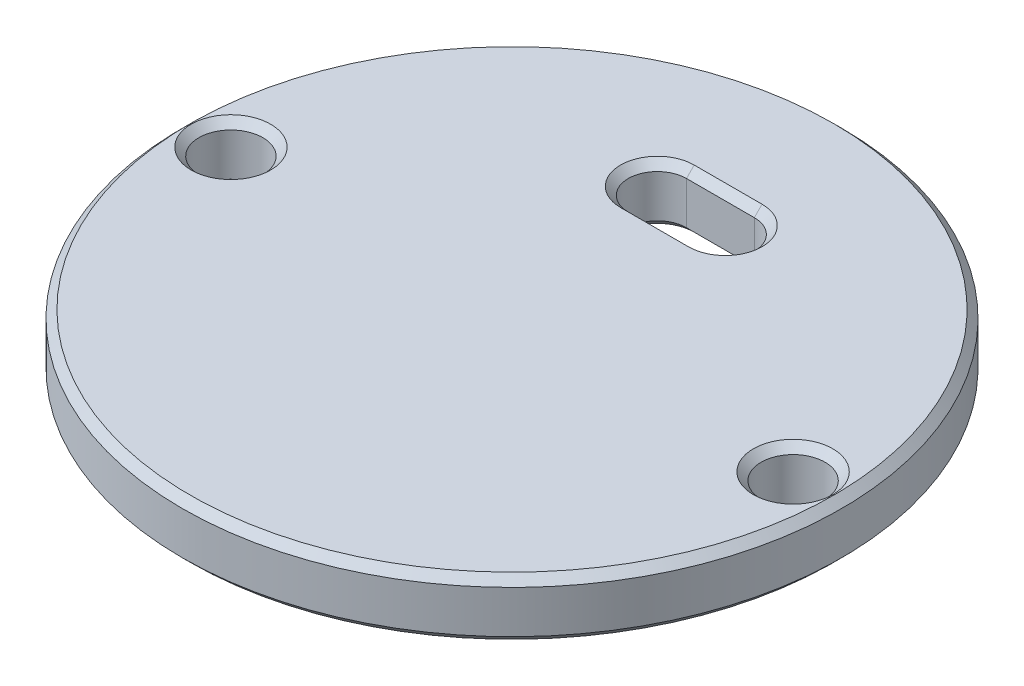
SolidWorks part; units mm, degrees
material "Pine"
ref_plane "Front Plane" through (0, 0, 0) normal (0, 0, 1) x (1, 0, 0)
ref_plane "Top Plane" through (0, 0, 0) normal (0, 1, 0) x (1, 0, 0)
ref_plane "Right Plane" through (0, 0, 0) normal (1, 0, 0) x (0, 0, -1)
sketch "Sketch1" plane through (0, 0, 0) normal (0, 1, 0) x (1, 0, 0)
  line L0 (-1.75, 9.083) -> (-1.75, 10.75) construction
  line L1 (-1.75, 7.75) -> (1.75, 7.75)
  line L2 (-1.75, 7.75) -> (-1.75, 9.083) construction
  line L3 (-1.75, 10.75) -> (1.75, 10.75)
  line L4 (1.75, 7.75) -> (1.75, 9.083) construction
  line L5 (-1.75, 7.75) -> (-0.2676, 9.0206) construction
  line L6 (-1.75, 10.75) -> (-0.2676, 9.4794) construction
  line L7 (-0.2676, 9.4794) -> (0, 9.25) construction
  line L8 (0.2676, 9.0206) -> (1.75, 7.75) construction
  line L9 (0, 9.25) -> (0.2676, 9.4794) construction
  line L10 (0.2676, 9.4794) -> (1.75, 10.75) construction
  line L11 (1.75, 9.083) -> (1.75, 10.75) construction
  line L12 (0, 9.25) -> (0.2676, 9.0206) construction
  line L13 (-0.2676, 9.0206) -> (0, 9.25) construction
  line L14 (-14.5, 0) -> (14.5, 0) construction
  circle A0 centre (0, 0) radius 17
  circle A1 centre (0, 0) radius 9.25 construction
  arc A2 (1.75, 7.75) -> (1.75, 10.75) centre (1.75, 9.25) ccw
  arc A3 (-1.75, 10.75) -> (-1.75, 7.75) centre (-1.75, 9.25) ccw
  arc A4 (-0.25, 9.2466) -> (-0.2676, 9.4794) centre (-1.75, 9.25) ccw construction
  arc A5 (-0.2676, 9.4794) -> (-1.75, 10.75) centre (-1.75, 9.25) ccw construction
  arc A6 (0.2676, 9.4794) -> (0.25, 9.2466) centre (1.75, 9.25) ccw construction
  arc A7 (1.75, 10.75) -> (0.2676, 9.4794) centre (1.75, 9.25) ccw construction
  arc A8 (0.25, 9.2466) -> (0.2676, 9.0206) centre (1.75, 9.25) ccw construction
  arc A9 (0.2676, 9.0206) -> (1.75, 7.75) centre (1.75, 9.25) ccw construction
  arc A10 (-0.2676, 9.0206) -> (-0.25, 9.2466) centre (-1.75, 9.25) ccw construction
  arc A11 (-1.75, 7.75) -> (-0.2676, 9.0206) centre (-1.75, 9.25) ccw construction
  circle A12 centre (-14.5, 0) radius 1.65
  circle A13 centre (14.5, 0) radius 1.65
  point P4 (0, 9.25)
  point P23 (0, 0)
  dimension "D1" = 34
  dimension "D2" = 18.5
  dimension "D5" = 3.3
  dimension "D3" = 3.5
  dimension "D4" = 3
  dimension "D6" = 29
extrude "Boss-Extrude1" add sketch "Sketch1" along normal blind 3
chamfer "Chamfer1" distance 0.4 angle 45 14 edges at (14.5, 0, 1.65) (14.5, 3, 1.65) (0, 3, -7.75) (3.25, 3, -9.25) (-3.25, 3, -9.25) (0, 3, -10.75) (0, 0, -7.75) (3.25, 0, -9.25) (-3.25, 0, -9.25) (0, 0, -10.75) (-14.5, 0, 1.65) (-14.5, 3, 1.65) (0, 0, 17) (0, 3, 17)
